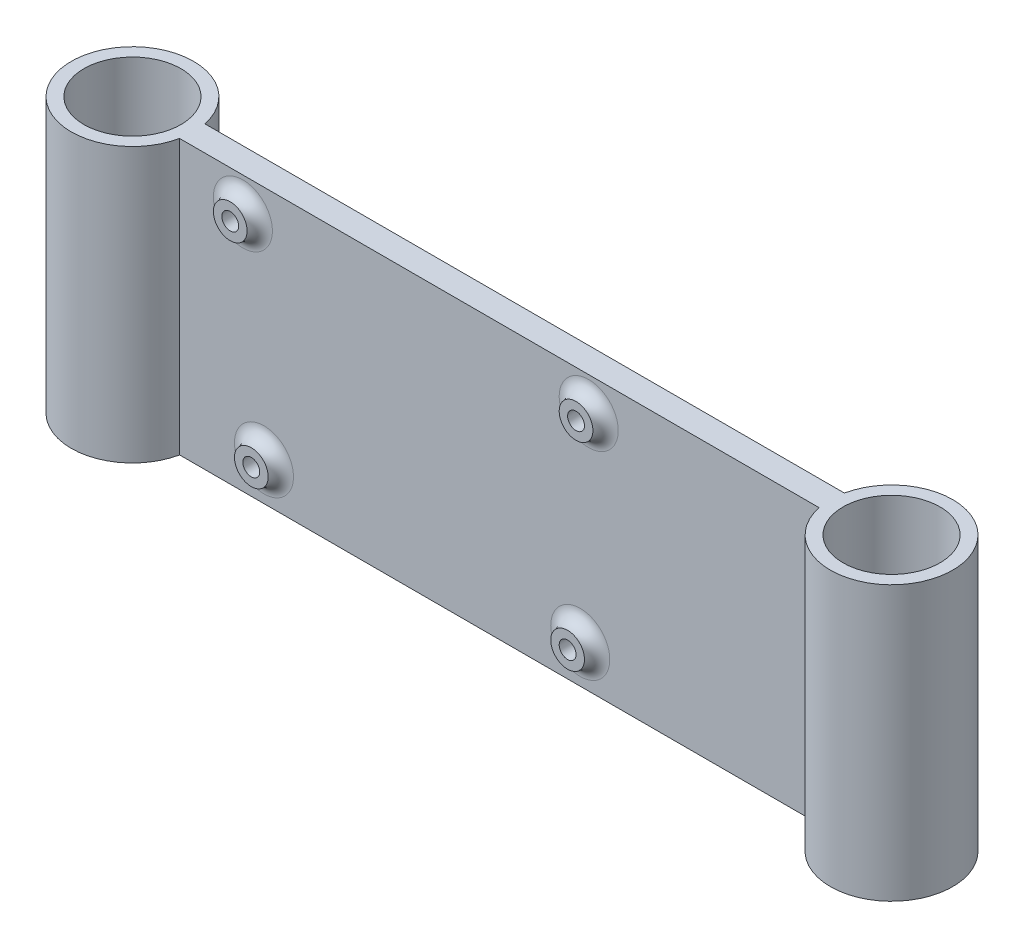
SolidWorks part; units mm, degrees
ref_plane "Front Plane" through (0, 0, 0) normal (0, 0, 1) x (1, 0, 0)
ref_plane "Top Plane" through (0, 0, 0) normal (0, 1, 0) x (1, 0, 0)
ref_plane "Right Plane" through (0, 0, 0) normal (1, 0, 0) x (0, 0, -1)
sketch "Sketch1" plane through (0, 0, 0) normal (0, 1, 0) x (1, 0, 0)
  line L0 (-28.3532, 3) -> (123.2743, 3)
  line L1 (-28.3532, -3) -> (123.2743, -3)
  line L2 (-31.0394, 0) -> (125.9606, 0) construction
  circle A0 centre (-42.5394, 0) radius 11.5
  circle A1 centre (137.4606, 0) radius 11.5
  arc A2 (-28.3532, -3) -> (-28.3532, 3) centre (-42.5394, 0) cw
  arc A3 (123.2743, 3) -> (123.2743, -3) centre (137.4606, 0) cw
  dimension "D3" = 23
  dimension "D4" = 23
  dimension "D5" = 180
  dimension "D6" = 3
  dimension "D7" = 3
  dimension "D1" = 6
  dimension "D2" = 3
extrude "Boss-Extrude1" add sketch "Sketch1" along normal blind 65
sketch "Sketch2" plane through (0, 0, 3) normal (0, 0, 1) x (1, 0, 0)
  line L0 (-28.3532, 65) -> (-28.3532, 0) construction
  line L1 (-28.3532, 65) -> (123.2743, 65) construction
  circle A0 centre (-13.3532, 57) radius 2
  circle A1 centre (-8.3532, 9) radius 2
  circle A2 centre (66.6468, 9) radius 2
  circle A3 centre (68.6468, 57) radius 2
  dimension "D1" = 4
  dimension "D6" = 82
  dimension "D2" = 15
  dimension "D3" = 8
  dimension "D4" = 5
  dimension "D5" = 48
  dimension "D7" = 75
extrude "Cut-Extrude1" cut sketch "Sketch2" against normal blind 10
sketch "Sketch3" plane through (0, 0, 3) normal (0, 0, 1) x (1, 0, 0)
  circle A0 centre (-13.3532, 57) radius 2
  circle A1 centre (-13.3532, 57) radius 4
  circle A2 centre (68.6468, 57) radius 2
  circle A3 centre (68.6468, 57) radius 4
  circle A4 centre (-8.3532, 9) radius 2
  circle A5 centre (-8.3532, 9) radius 4
  circle A6 centre (66.6468, 9) radius 2
  circle A7 centre (66.6468, 9) radius 4
  dimension "D1" = 2
extrude "Boss-Extrude2" add sketch "Sketch3" along normal blind 3
fillet "Fillet1" radius 3 4 edges at (64.6468, 57, 3) (62.6468, 9, 3) (-12.3532, 9, 3) (-17.3532, 57, 3)
